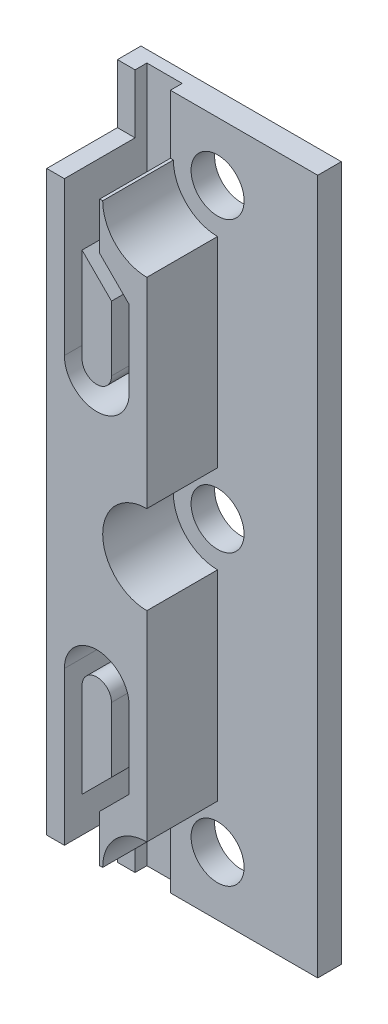
SolidWorks part; units mm, degrees
ref_plane "Plan de face" through (0, 0, 0) normal (0, 0, 1) x (1, 0, 0)
ref_plane "Plan de dessus" through (0, 0, 0) normal (0, 1, 0) x (1, 0, 0)
ref_plane "Plan de droite" through (0, 0, 0) normal (1, 0, 0) x (0, 0, -1)
sketch "Esquisse1" plane through (0, 0, 0) normal (0, 0, 1) x (1, 0, 0)
  line L1 (0, 0) -> (17, 0)
  line L2 (0, 0) -> (0, -59)
  line L3 (0, -59) -> (17, -59)
  line L4 (17, 0) -> (17, -59)
  dimension "D1" = 17
  dimension "D2" = 59
extrude "Boss.-Extru.1" add sketch "Esquisse1" along normal blind 2
sketch "Esquisse2" plane through (0, 0, 2) normal (0, 0, 1) x (1, 0, 0)
  line L0 (0, -59) -> (17, -59) construction
  line L1 (0, 0) -> (8.5, 0)
  line L2 (0, 0) -> (0, -59)
  line L3 (0, -59) -> (8.5, -59)
  line L4 (8.5, 0) -> (8.5, -59)
  line L5 (8.5, -54) -> (0, -54)
  line L6 (8.5, -5) -> (0, -5)
  dimension "D1" = 5
  dimension "D2" = 5
extrude "Boss.-Extru.2" add sketch "Esquisse2" along normal blind 6 contours L4 L6 L2 L5 region at (4.25, -29.5, 2)
sketch "Esquisse4" plane through (0, 0, 8) normal (0, 0, 1) x (1, 0, 0)
  line L0 (8.5, -5) -> (8.5, -54) construction
  circle A0 centre (8.5, -54) radius 2.25
  circle A1 centre (8.5, -29.5) radius 2.25
  circle A2 centre (8.5, -5) radius 2.25
  dimension "D1" = 4.5
  dimension "D2" = 4.5
  dimension "D3" = 4.5
extrude "Enlèv. mat.-Extru.6" cut sketch "Esquisse4" against normal blind 27
sketch "Esquisse3" plane through (0, 0, 8) normal (0, 0, 1) x (1, 0, 0)
  line L0 (3, -41.5) -> (5.5, -41.5)
  line L1 (0, -5) -> (0, -54) construction
  line L2 (1.5, -61) -> (1.5, -41)
  line L3 (1.5, -41) -> (3, -41)
  line L4 (3, -61) -> (3, -41)
  line L7 (3, -61) -> (3, -41)
  line L8 (3, -41) -> (4.5, -41)
  line L9 (4.5, -61) -> (4.5, -41)
  line L11 (4.5, -61) -> (4.5, -41)
  line L12 (4.5, -41) -> (7, -41)
  line L13 (7, -61) -> (7, -41)
  line L14 (5.5, -47) -> (3, -49.5)
  line L15 (8.5, -5) -> (8.5, -54) construction
  line L16 (4.25, -38.25) -> (4.25, -41)
  line L17 (5.5, -41) -> (7, -41)
  line L18 (5.5, -41) -> (5.5, -47)
  line L19 (1.5, -61) -> (3, -61)
  line L20 (7, -41) -> (7, -47.5)
  line L21 (7, -47.5) -> (4.5, -50)
  line L22 (3, -61) -> (4.5, -61)
  line L23 (4.5, -61) -> (7, -61)
  arc A0 (1.5, -41) -> (7, -41) centre (4.25, -41) cw
  arc A1 (3, -41.5) -> (5.5, -41.5) centre (4.25, -41.5) cw
  line M62 (0, -54) -> (6.25, -54)
  dimension "D5" = 1.5
  dimension "D8" = 1.5
  dimension "D9" = 45
  dimension "D7" = 0.5
  dimension "D2" = 1.5
  dimension "D3" = 1.5
  dimension "D4" = 1.5
  dimension "D6" = 1.25
  dimension "D10" = 1.5
  dimension "D11" = 20
  dimension "D12" = 13
  dimension "D13" = 45
  dimension "D14" = 2.5
extrude "Enlèv. mat.-Extru.7" cut sketch "Esquisse3" against normal blind 7 contours L2 L19 L4 M62 | L4 L22 L9 M62 | L9 L11 L14 L4 M62 | L4 L7 L3 L2 M62 | L21 L13 L12 L18 L14 L11 | L16 L12 A0 | L3 L16 A0 | L4 A1 L8 | L12 A1 L18 region at (2.25, -47.5, 8) region at (3.0311, -41.1239, 8) region at (3.7857, -51.3571, 8) region at (2.9999, -39.733, 8) region at (5.4689, -41.1239, 8) region at (6.034, -45.2379, 8) region at (3.75, -57.5, 8) region at (2.25, -57.5, 8) region at (5.5001, -39.733, 8)
ref_plane "Plan1" through (0, -29.5, 0) normal (0, 1, 0) x (1, 0, 0)
mirror "Symétrie1" about plane through (0, -29.5, 0) normal (0, 1, 0) of "Enlèv. mat.-Extru.7"
sketch "Esquisse5" plane through (0, 0, 8) normal (0, 0, 1) x (1, 0, 0)
  circle A0 centre (8.5, -29.5) radius 3.75
  circle A1 centre (8.5, -5) radius 3.75
  circle A2 centre (8.5, -54) radius 3.75
  dimension "D1" = 7.5
  dimension "D2" = 7.5
  dimension "D3" = 7.5
extrude "Enlèv. mat.-Extru.8" cut sketch "Esquisse5" against normal blind 6
